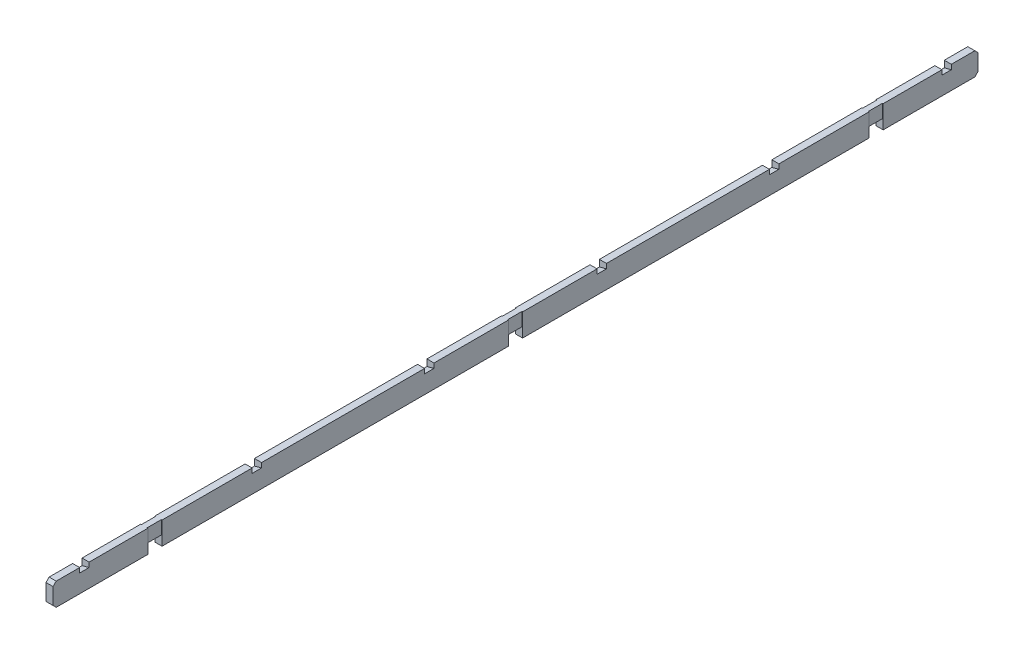
SolidWorks part; units mm, degrees
ref_plane "Front" through (0, 0, 0) normal (0, 0, 1) x (1, 0, 0)
ref_plane "Top" through (0, 0, 0) normal (0, 1, 0) x (1, 0, 0)
ref_plane "Right" through (0, 0, 0) normal (1, 0, 0) x (0, 0, -1)
sketch "Esquisse1" plane through (0, 0, 0) normal (0, 0, 1) x (1, 0, 0)
  line L1 (0, 0) -> (45, 0)
  line L2 (0, 0) -> (0, 145)
  line L3 (0, 145) -> (45, 145)
  line L4 (45, 0) -> (45, 145)
  dimension "D1" = 45
  dimension "D2" = 145
extrude "Boss.-Extru.1" add sketch "Esquisse1" along normal blind 5900
sketch "Esquisse2" plane through (0, 0, 5900) normal (0, 0, 1) x (1, 0, 0)
  line L0 (0, 102.9423) -> (45, 115)
  line L1 (0, 145) -> (0, 0) construction
  line L2 (45, 0) -> (45, 145) construction
  line L3 (45, 115) -> (45, 145)
  line L4 (45, 145) -> (0, 145)
  line L5 (0, 145) -> (0, 102.9423)
  dimension "D1" = 30
  dimension "D2" = 75
extrude "Enlèv. mat.-Extru.1" cut sketch "Esquisse2" against normal blind 60 from offset 170 offset against normal yes
pattern_linear "Répétition linéaire1" count 6 spacing 1100 along (0, 0, -1) of "Enlèv. mat.-Extru.1"
chamfer "Chanfrein1" distance 20 angle 45 4 edges at (22.5, 0, 5900) (22.5, 145, 5900) (22.5, 0, 0) (22.5, 145, 0)
sketch "Esquisse3" plane through (0, 0, 0) normal (-1, 0, 0) x (0, 0, 1)
  line L0 (2950, 0) -> (2950, 145) construction
  line L1 (5880, 0) -> (20, 0) construction
  line L2 (3470, 145) -> (2430, 145) construction
  line L3 (1270, 145) -> (230, 145) construction
  line L4 (605, 145) -> (695, 145)
  line L5 (605, 145) -> (605, 0)
  line L6 (605, 0) -> (695, 0)
  line L7 (695, 145) -> (695, 0)
  line L8 (2995, 145) -> (2905, 145)
  line L9 (2905, 145) -> (2905, 0)
  line L10 (2905, 0) -> (2995, 0)
  line L11 (2995, 145) -> (2995, 0)
  line L12 (5205, 145) -> (5205, 0)
  line L13 (5295, 0) -> (5205, 0)
  line L14 (5295, 145) -> (5295, 0)
  line L15 (5295, 145) -> (5205, 145)
  dimension "D1" = 90
  dimension "D2" = 2300
extrude "Enlèv. mat.-Extru.2" cut sketch "Esquisse3" against normal blind 4.5
extrude "Enlèv. mat.-Extru.3" cut sketch "Esquisse3<2>" along normal blind 4.5 from vertex starting at point (45, 145, 20)
sketch "Esquisse3<2>" plane through (0, 0, 0) normal (-1, 0, 0) x (0, 0, 1) same geometry as "Esquisse3"
sketch "Esquisse4" plane through (4.5, 0, 0) normal (-1, 0, 0) x (0, 0, 1)
  line L0 (695, 0) -> (695, 145) construction
  line L1 (605, 0) -> (695, 0)
  line L2 (605, 0) -> (605, 60)
  line L3 (605, 60) -> (695, 60)
  line L4 (695, 0) -> (695, 60)
  line L5 (2995, 0) -> (2995, 145) construction
  line L6 (2905, 0) -> (2995, 0)
  line L7 (2905, 0) -> (2905, 60)
  line L8 (2905, 60) -> (2995, 60)
  line L9 (2995, 0) -> (2995, 60)
  line L10 (5295, 0) -> (5295, 145) construction
  line L11 (5205, 0) -> (5295, 0)
  line L12 (5205, 0) -> (5205, 60)
  line L13 (5205, 60) -> (5295, 60)
  line L14 (5295, 0) -> (5295, 60)
  dimension "D1" = 60
extrude "Enlèv. mat.-Extru.4" cut sketch "Esquisse4" against normal through all
